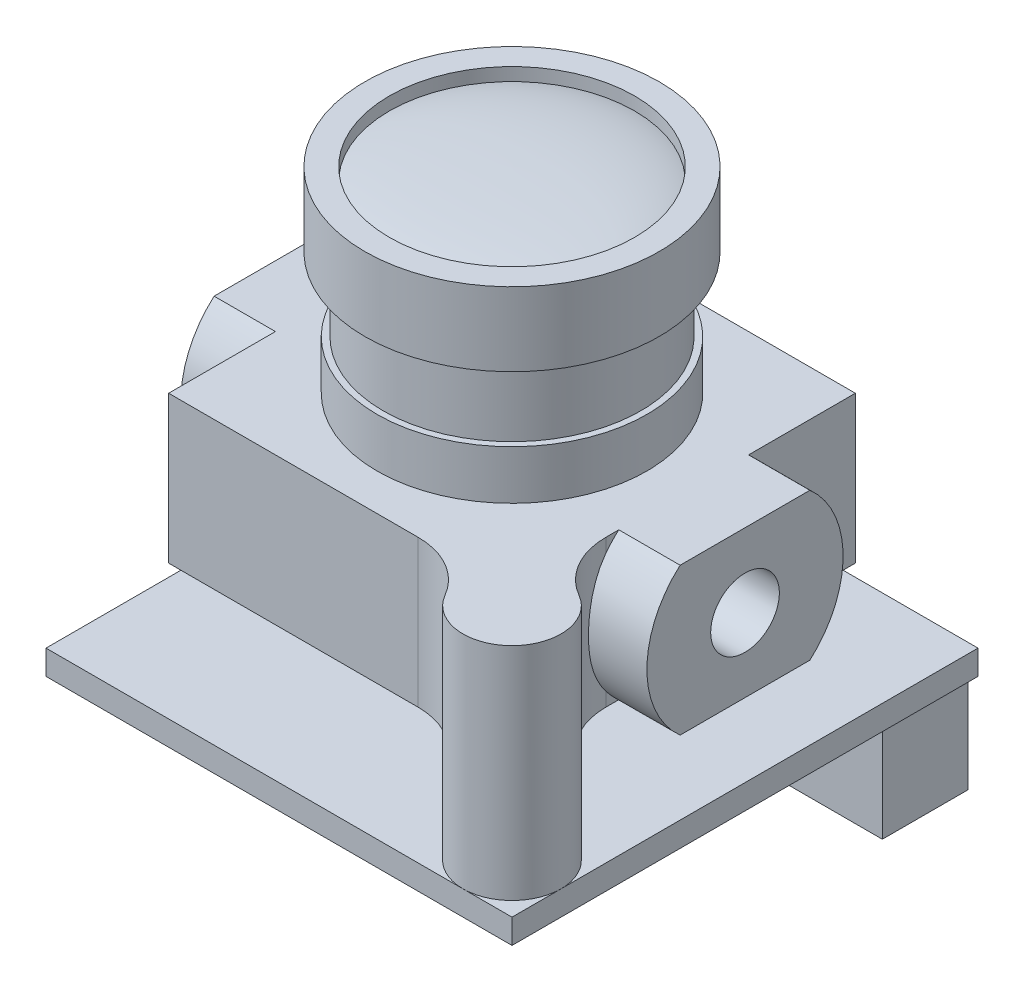
SolidWorks part; units mm, degrees
ref_plane "Front Plane" through (0, 0, 0) normal (0, 0, 1) x (1, 0, 0)
ref_plane "Top Plane" through (0, 0, 0) normal (0, 1, 0) x (1, 0, 0)
ref_plane "Right Plane" through (0, 0, 0) normal (1, 0, 0) x (0, 0, -1)
sketch "Sketch1" plane through (0, 0, 0) normal (0, 1, 0) x (1, 0, 0)
  line L1 (-9.5, 9.5) -> (9.5, 9.5)
  line L2 (-9.5, 9.5) -> (-9.5, -9.5)
  line L3 (-9.5, -9.5) -> (9.5, -9.5)
  line L4 (9.5, 9.5) -> (9.5, -9.5)
  line L5 (-9.5, 9.5) -> (9.5, -9.5) construction
  line L6 (-9.5, -9.5) -> (9.5, 9.5) construction
  point P0 (0, 0)
  dimension "D1" = 19
extrude "Boss-Extrude1" add sketch "Sketch1" along normal blind 1
sketch "Sketch2" plane through (0, 1, 0) normal (0, 1, 0) x (1, 0, 0)
  line L0 (9.5, 9.5) -> (-9.5, 9.5) construction
  line L1 (-9.5, 9.5) -> (-9.5, -9.5) construction
  line L2 (-9.5, -9.5) -> (9.5, 9.5) construction
  circle A0 centre (-7.5, 7.5) radius 2
  circle A1 centre (7.5, -7.5) radius 2
  dimension "D1" = 4
extrude "Boss-Extrude2" add sketch "Sketch2" along normal blind 3
sketch "Sketch3" plane through (0, 4, 0) normal (0, 1, 0) x (1, 0, 0)
  line L1 (7, -7) -> (-7, -7)
  line L2 (7, -7) -> (7, 7)
  line L3 (7, 7) -> (-7, 7)
  line L4 (-7, -7) -> (-7, 7)
  line L5 (7, -7) -> (-7, 7) construction
  line L6 (7, 7) -> (-7, -7) construction
  circle A0 centre (7.5, -7.5) radius 2 construction
  circle A1 centre (-7.5, 7.5) radius 2 construction
  circle A2 centre (7.5, -7.5) radius 2
  circle A3 centre (-7.5, 7.5) radius 2
  point P6 (0, 0)
  dimension "D1" = 14
extrude "Boss-Extrude3" add sketch "Sketch3" along normal blind 6 contours A3 | L4 L3 L2 L1 | A2
sketch "Sketch4" plane through (-7, 0, 0) normal (-1, 0, 0) x (0, 0, 1)
  line L0 (7, 7) -> (-9.5, 7) construction
  line L1 (7, 10) -> (7, 4) construction
  line L2 (-9.5, 10) -> (-9.5, 1) construction
  line L3 (0, 0) -> (0, 10) construction
  line L4 (7, 10) -> (-5.5635, 10) construction
  line L5 (7, 4) -> (-5.5635, 4) construction
  line L6 (4, 10) -> (-4, 10)
  line L7 (4, 10) -> (4, 4)
  line L8 (4, 4) -> (-4, 4)
  line L9 (-4, 10) -> (-4, 4)
  line L10 (4, 10) -> (-4, 4) construction
  line L11 (4, 4) -> (-4, 10) construction
  circle A0 centre (0, 7) radius 4
  circle A1 centre (0, 7) radius 1.4
  point P11 (0, 7)
  dimension "D2" = 2.8
  dimension "D1" = 8
extrude "Boss-Extrude4" add sketch "Sketch4" along normal up to surface (2.5 mm away) contours L6 A0 L8 A1 region at (-7, 8.6046, 3.5546) up to face at (-9.5, 0.6, -1.5)
sketch "Sketch5" plane through (7, 0, 0) normal (1, 0, 0) x (0, 0, -1)
  line L2 (-2.6458, 4) -> (2.6458, 4)
  line L3 (2.6458, 10) -> (-2.6458, 10)
  line L4 (-2.6458, 4) -> (2.6458, 4)
  line L5 (2.6458, 10) -> (-2.6458, 10)
  circle A0 centre (0, 7) radius 1.4 construction
  circle A1 centre (0, 7) radius 1.4
  arc A2 (2.6458, 4) -> (2.6458, 10) centre (0, 7) ccw
  arc A3 (-2.6458, 10) -> (-2.6458, 4) centre (0, 7) ccw
  arc A4 (2.6458, 4) -> (2.6458, 10) centre (0, 7) ccw
  arc A5 (-2.6458, 10) -> (-2.6458, 4) centre (0, 7) ccw
  dimension "D1" = 0
extrude "Boss-Extrude5" add sketch "Sketch5" along normal up to surface (2.5 mm away) up to face at (9.5, 0.6, 1.5)
sketch "Sketch6" plane through (0, 10, 0) normal (0, 1, 0) x (1, 0, 0)
  circle A0 centre (0, 0) radius 5.5
  dimension "D1" = 11
extrude "Boss-Extrude6" add sketch "Sketch6" along normal blind 2
sketch "Sketch7" plane through (0, 12, 0) normal (0, 1, 0) x (1, 0, 0)
  circle A0 centre (0, 0) radius 5.25
  dimension "D1" = 10.5
extrude "Boss-Extrude7" add sketch "Sketch7" along normal blind 3
sketch "Sketch8" plane through (0, 15, 0) normal (0, 1, 0) x (1, 0, 0)
  circle A0 centre (0, 0) radius 6
  dimension "D1" = 12
extrude "Boss-Extrude8" add sketch "Sketch8" along normal blind 3
ref_axis "Axis1" through (0, 18.9, 0) along (0, -1, 0)
sketch "Sketch11" plane through (0, 0, 0) normal (0, 0, 1) x (1, 0, 0)
  line L0 (-4.9987, 18) -> (-4.9987, 17.4688)
  line L1 (6, 18) -> (-6, 18) construction
  line L2 (0, 18) -> (0, 0) construction
  line L3 (0, 17.9677) -> (0, 18)
  line L4 (0, 18) -> (-4.9987, 18)
  spline S0 degree 2 poles (-4.9987, 17.4688) (-3.5687, 17.9482) (0, 17.9677) knots 0 0 0 1 1 1
revolve "Cut-Revolve3" cut sketch "Sketch11" angle 360 about L2 region at (-3.5835, 17.8608, 0)
sketch "Sketch12" plane through (0, 0, 0) normal (0, -1, 0) x (1, 0, 0)
  line L0 (-9.5, 9.5) -> (9.5, 9.5) construction
  line L1 (-9.3, 9.3) -> (-0.3, 9.3)
  line L2 (-9.3, 9.3) -> (-9.3, 5.8)
  line L3 (-9.3, 5.8) -> (-0.3, 5.8)
  line L4 (-0.3, 9.3) -> (-0.3, 5.8)
  line L5 (-9.3, 9.3) -> (-9.5, 9.3) construction
  line L6 (-9.5, -9.5) -> (-9.5, 9.5) construction
  line L7 (-9.3, 9.3) -> (-9.3, 9.5) construction
  line L8 (9.3, -9.3) -> (9.3, -9.5) construction
  line L9 (9.3, -9.3) -> (0.3, -9.3)
  line L10 (9.3, -9.3) -> (9.3, -5.8)
  line L11 (9.3, -5.8) -> (0.3, -5.8)
  line L12 (0.3, -9.3) -> (0.3, -5.8)
  line L13 (9.5, -9.5) -> (-9.5, -9.5) construction
  line L14 (9.3, -9.3) -> (9.5, -9.3) construction
  line L15 (9.5, 9.5) -> (9.5, -9.5) construction
  dimension "D1" = 9
  dimension "D2" = 3.5
  dimension "D3" = 0.2
extrude "Boss-Extrude9" add sketch "Sketch12" along normal blind 4 contours L12 L9 L10 L11 region at (4.8, 0, -7.55)
fillet "Fillet1" radius 3 4 edges at (-7, 7, -5.5635) (-5.5635, 7, -7) (7, 7, 5.5635) (5.5635, 7, 7)
sketch "Sketch14" plane through (0, 12, 0) normal (0, 1, 0) x (1, 0, 0)
  circle A0 centre (0, 0) radius 5.25 construction
  circle A1 centre (0, 0) radius 5.25
extrude "Boss-Extrude11" add sketch "Sketch14" along normal blind 0.5 separate body
